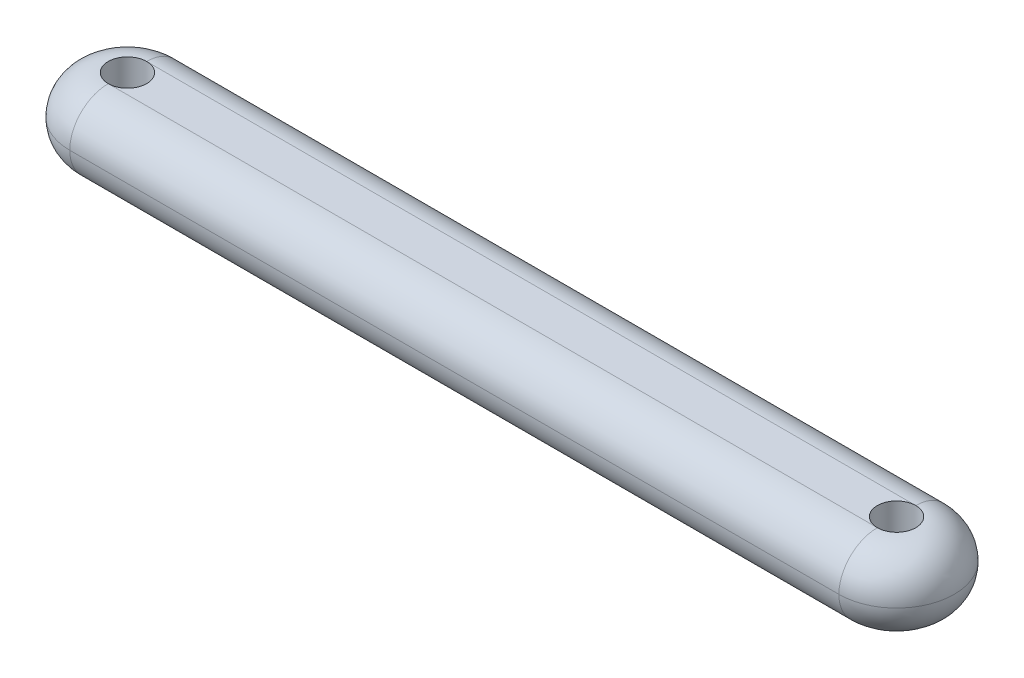
SolidWorks part; units mm, degrees
ref_plane "Alzado" through (0, 0, 0) normal (1, 0, 0) x (0, 1, 0)
ref_plane "Planta" through (0, 0, 0) normal (0, 0, 1) x (0, 1, 0)
ref_plane "Vista lateral" through (0, 0, 0) normal (0, 1, 0) x (-1, 0, 0)
sketch "Croquis1" plane through (0, 0, 0) normal (0, 1, 0) x (-1, 0, 0)
  line L0 (0, 0) -> (100, 0) construction
  line L1 (0, 0) -> (100, 0) construction
  line L2 (0, 7.5) -> (100, 7.5)
  line L3 (0, -7.5) -> (100, -7.5)
  arc A0 (0, 7.5) -> (0, -7.5) centre (0, 0) ccw
  arc A1 (100, -7.5) -> (100, 7.5) centre (100, 0) ccw
  circle A2 centre (0, 0) radius 2.5
  circle A3 centre (100, 0) radius 2.5
  point P3 (50, 0)
  dimension "D3" = 5
  dimension "D1" = 100
  dimension "D2" = 15
extrude "Saliente-Extruir1" add sketch "Croquis1" along normal mid plane 10
fillet "Redondeo1" radius 5 8 edges at (7.5, 5, 0) (-50, 5, 7.5) (-107.5, 5, 0) (7.5, -5, 0) (-50, -5, 7.5) (-107.5, -5, 0) (-50, 5, -7.5) (-50, -5, -7.5)
equation "\"ancho\"= 15"
equation "\"esp\"= 10"
equation "\"Lbarra05\"=100"
equation "\"agujeros\"= 5"
equation "\"D1@Croquis1\"=\"Lbarra05\""
equation "\"D2@Croquis1\"=\"ancho\""
equation "\"D3@Croquis1\"=\"agujeros\""
equation "\"D1@Saliente-Extruir1\"=\"esp\""
equation "\"D1@Redondeo1\"=\"esp\"/2"
